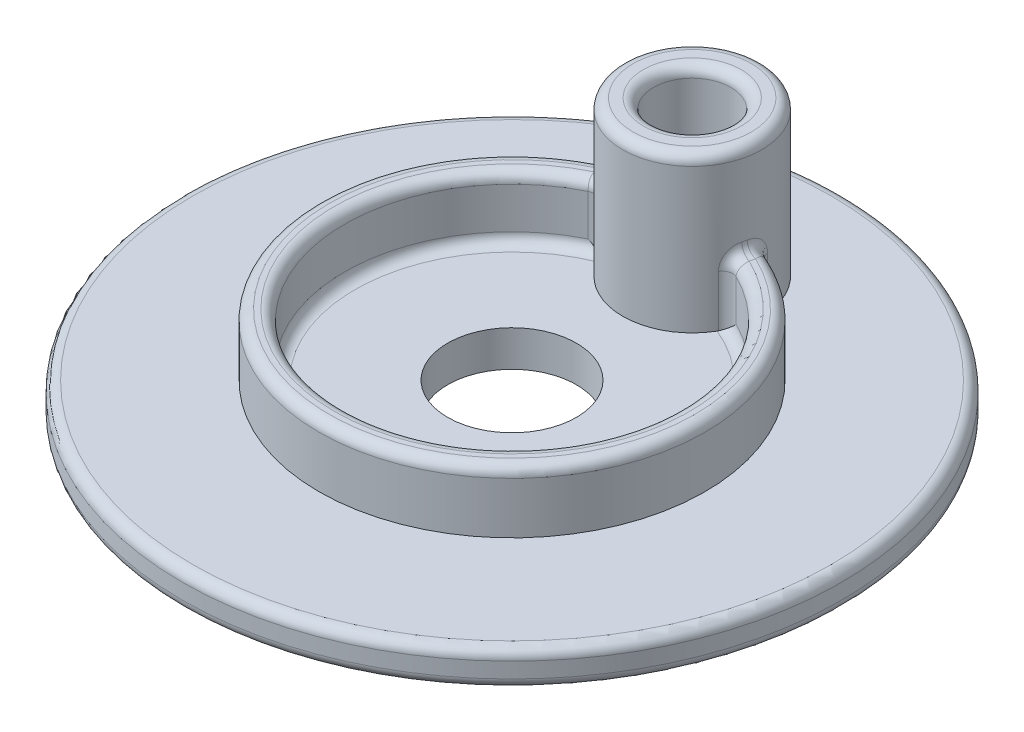
SolidWorks part; units mm, degrees
ref_plane "Front Plane" through (0, 0, 0) normal (0, 0, 1) x (1, 0, 0)
ref_plane "Top Plane" through (0, 0, 0) normal (0, 1, 0) x (1, 0, 0)
ref_plane "Right Plane" through (0, 0, 0) normal (1, 0, 0) x (0, 0, -1)
sketch "Sketch1" plane through (0, 0, 0) normal (0, 1, 0) x (1, 0, 0)
  circle A0 centre (0, 0) radius 64
  dimension "D1" = 128
extrude "Boss-Extrude1" add sketch "Sketch1" along normal blind 7
sketch "Sketch2" plane through (0, 7, 0) normal (0, 1, 0) x (1, 0, 0)
  circle A0 centre (0, 0) radius 37.5
  circle A1 centre (0, 0) radius 32.5
  dimension "D1" = 75
  dimension "D2" = 5
extrude "Boss-Extrude2" add sketch "Sketch2" along normal blind 12
sketch "Sketch3" plane through (0, 7, 0) normal (0, 1, 0) x (1, 0, 0)
  circle A0 centre (0, 0) radius 12.5
  dimension "D1" = 25
extrude "Cut-Extrude1" cut sketch "Sketch3" against normal through all
fillet "Fillet1" radius 2 4 edges at (0, 0, 64) (0, 7, 64) (0, 19, 32.5) (0, 19, 37.5)
sketch "Sketch10" plane through (0, 19, 0) normal (0, 1, 0) x (1, 0, 0)
  line L0 (0, 35.5) -> (0, 37.5) construction
  line L1 (0, 0) -> (0, 35) construction
  circle A0 centre (0, 0) radius 35.5 construction
  circle A1 centre (0, 0) radius 37.5 construction
  circle A2 centre (0, 35) radius 13.5
  dimension "D1" = 27
  dimension "D2" = 35
extrude "Boss-Extrude3" add sketch "Sketch10" along normal blind 18 and the other way blind 12
sketch "Sketch12" plane through (0, 37, 0) normal (0, 1, 0) x (1, 0, 0)
  circle A0 centre (0, 35) radius 7.5
  dimension "D1" = 15
extrude "Cut-Extrude2" cut sketch "Sketch12" against normal through all
fillet "Fillet2" radius 2 14 edges at (12.6903, 18.2486, -30.3948) (13.2469, 19, -32.3981) (13.4847, 18.4187, -34.3583) (-12.7454, 18.4302, -30.5498) (-13.2469, 19, -32.3981) (-13.493, 18.1927, -34.5652) (-12.5342, 12, -29.9857) (0, 7, 32.5) (12.5342, 12, -29.9857) (0, 37, -21.5) (0, 37, -27.5) (13.5, 12, -34.9857) (-13.5, 12, -34.9857) (0, 0, -27.5)
